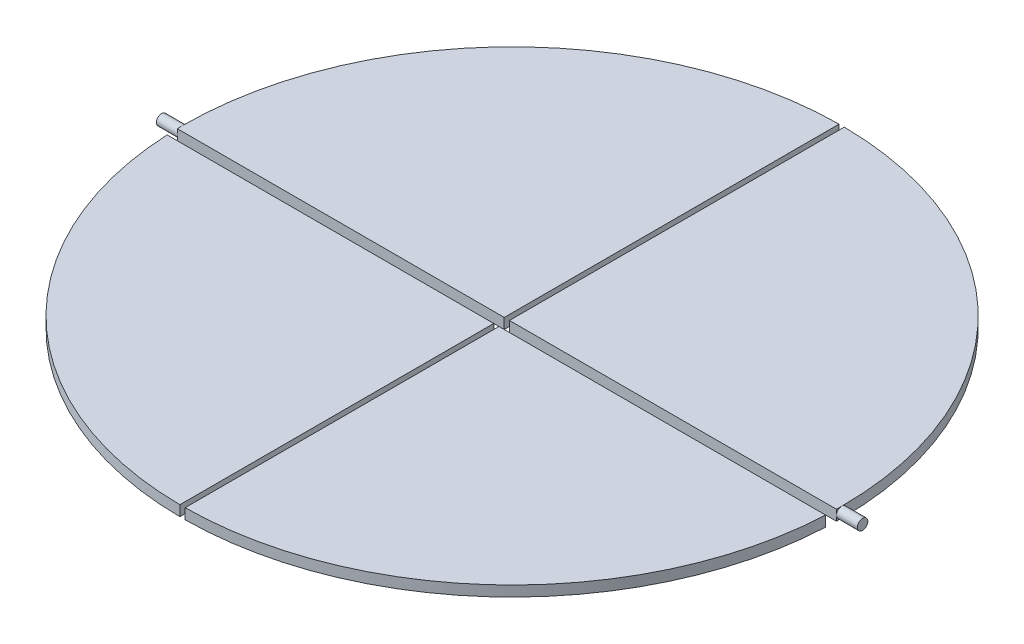
SolidWorks part; units mm, degrees
ref_plane "Спереди" through (0, 0, 0) normal (0, 0, 1) x (1, 0, 0)
ref_plane "Сверху" through (0, 0, 0) normal (0, 1, 0) x (1, 0, 0)
ref_plane "Справа" through (0, 0, 0) normal (1, 0, 0) x (0, 0, -1)
sketch "Эскиз1" plane through (0, 0, 0) normal (0, 1, 0) x (1, 0, 0)
  circle A0 centre (0, 0) radius 63
extrude "Бобышка-Вытянуть1" add sketch "Эскиз1" along normal blind 2
sketch "Эскиз4" plane through (0, 0, 0) normal (1, 0, 0) x (0, 0, -1)
  circle A0 centre (0, 1) radius 1
extrude "Бобышка-Вытянуть2" add sketch "Эскиз4" along normal blind 67 and the other way blind 67
sketch "Эскиз5" plane through (0, 2, 0) normal (0, 1, 0) x (1, 0, 0)
  line L0 (-62.9921, -1) -> (-64.3746, -1)
  line L1 (-67, -1) -> (-62.9921, -1) construction
  line L2 (-64.3746, -1) -> (-64.3746, -3)
  line L3 (-64.3746, -3) -> (64.485, -3)
  line L4 (64.485, -3) -> (64.485, -1)
  line L5 (62.9921, -1) -> (67, -1) construction
  line L6 (64.485, -1) -> (-64.3746, -1)
  arc M5 (-63, 0) -> (63, 0) centre (0, 0) ccw
extrude "Вырез-Вытянуть2" cut sketch "Эскиз5" against normal through all contours L6 L3 M5 region at (0, 2, 1.9998)
sketch "Эскиз8" plane through (0, 2, 0) normal (0, 1, 0) x (1, 0, 0)
  line L1 (0, 66.1906) -> (-0.5, 66.1906)
  line L2 (0, 66.1906) -> (0.5, 66.1906)
  line L3 (-0.5, 66.1906) -> (-0.5, -2.0251)
  line L4 (-0.5, -2.0251) -> (0.5, -2.0251)
  line L5 (0.5, -2.0251) -> (0.5, 66.1906)
extrude "Вырез-Вытянуть4" cut sketch "Эскиз8" against normal through all
sketch "Эскиз9" plane through (0, 2, 0) normal (0, 1, 0) x (1, 0, 0)
  line L0 (-0.5, -1) -> (-0.5, -76.0886)
  line L1 (-0.5, -76.0886) -> (0.5, -76.0886)
  line L2 (0.5, -76.0886) -> (0.5, -1)
  line L3 (0.5, -1) -> (-0.5, -1)
extrude "Вырез-Вытянуть5" cut sketch "Эскиз9" against normal through all
